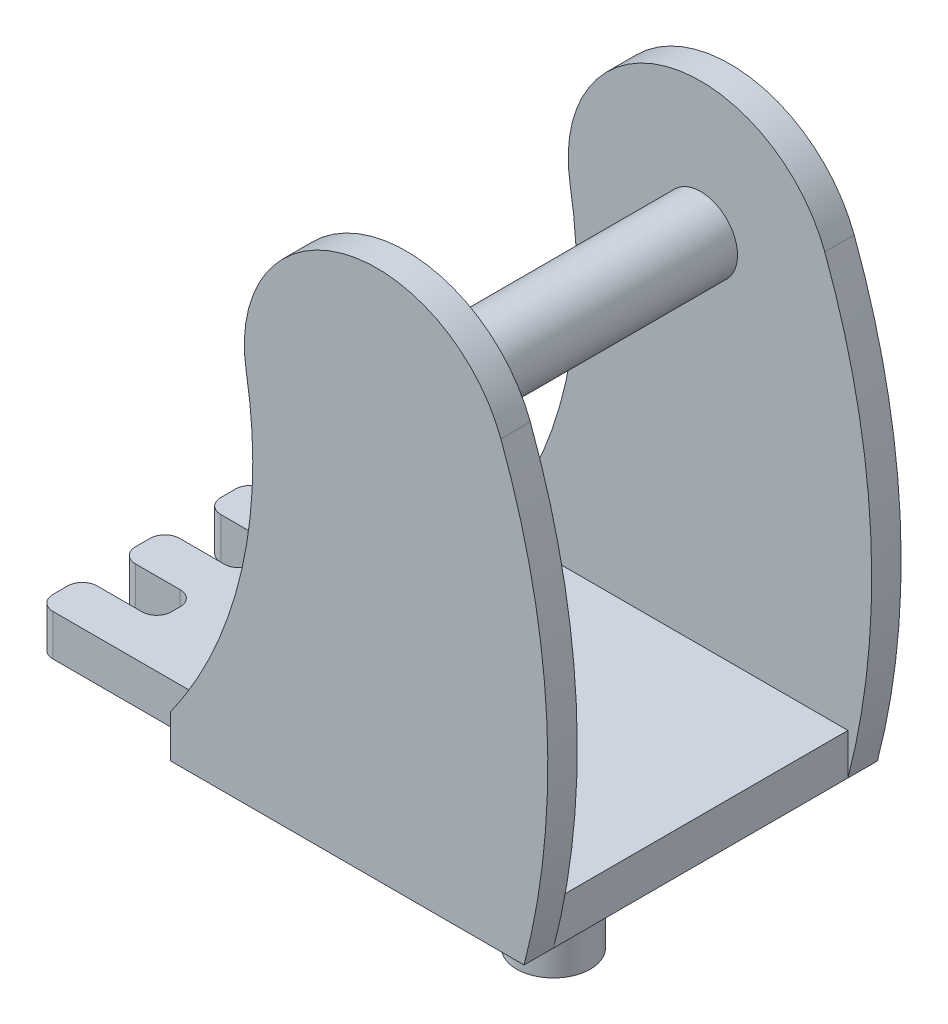
SolidWorks part; units mm, degrees
ref_plane "Front Plane" through (0, 0, 0) normal (0, 0, 1) x (1, 0, 0)
ref_plane "Top Plane" through (0, 0, 0) normal (0, 1, 0) x (1, 0, 0)
ref_plane "Right Plane" through (0, 0, 0) normal (1, 0, 0) x (0, 0, -1)
sketch "Sketch1" plane through (0, 0, 0) normal (0, 0, 1) x (1, 0, 0)
  circle A0 centre (0, 0) radius 12.5
  dimension "D1" = 25
extrude "Boss-Extrude1" add sketch "Sketch1" along normal mid plane 100
sketch "Sketch2" plane through (0, 0, 50) normal (0, 0, 1) x (1, 0, 0)
  line L0 (0, 0) -> (0, -135) construction
  line L1 (0, -135) -> (50, -135)
  line L2 (0, -135) -> (-70, -135)
  line L3 (-70, -120.4597) -> (-70, -135)
  arc A0 (42.1321, 15.8077) -> (-44.3389, -7.6849) centre (0, 0) ccw
  arc A1 (50, -135) -> (42.1321, 15.8077) centre (-191.9352, -72.013) ccw
  arc A2 (-44.3389, -7.6849) -> (-70, -120.4597) centre (-192.2863, -33.3275) cw
  dimension "D1" = 90
  dimension "D5" = 250
  dimension "D2" = 135
  dimension "D3" = 50
  dimension "D4" = 70
extrude "Boss-Extrude2" add sketch "Sketch2" along normal blind 10
ref_axis "Axis1" through (0, 0, 50) along (0, 0, -1)
mirror "Mirror1" about plane through (0, 0, 0) normal (0, 0, 1) of "Boss-Extrude2"
ref_plane "Plane1" through (0, -135, 0) normal (0, -1, 0) x (-1, 0, 0)
sketch "Sketch3" plane through (0, -135, 0) normal (0, -1, 0) x (-1, 0, 0)
  line L0 (120, 7) -> (104.7741, 7)
  line L1 (99.7741, 2) -> (99.7741, -2)
  line L2 (120, 50) -> (-50, 50)
  line L3 (120, -50) -> (-50, -50)
  line L4 (-50, 50) -> (-50, -50)
  line L5 (125, 45) -> (125, 40)
  line L7 (120, -7) -> (104.7741, -7)
  line L8 (120, 35) -> (104.7741, 35)
  line L10 (120, 22) -> (104.7741, 22)
  line L11 (99.7741, 30) -> (99.7741, 27)
  line L12 (99.7741, -27) -> (99.7741, -30)
  line L14 (120, -35) -> (104.7741, -35)
  line L15 (120, -22) -> (104.7741, -22)
  line L16 (125, 17) -> (125, 12)
  line L17 (125, -12) -> (125, -17)
  line L18 (125, -40) -> (125, -45)
  arc A0 (120, -50) -> (125, -45) centre (120, -45) ccw
  arc A1 (125, -40) -> (120, -35) centre (120, -40) ccw
  arc A2 (99.7741, -30) -> (104.7741, -35) centre (104.7741, -30) ccw
  arc A3 (99.7741, -27) -> (104.7741, -22) centre (104.7741, -27) cw
  arc A4 (125, -17) -> (120, -22) centre (120, -17) cw
  arc A5 (125, -12) -> (120, -7) centre (120, -12) ccw
  arc A6 (99.7741, -2) -> (104.7741, -7) centre (104.7741, -2) ccw
  arc A7 (104.7741, 7) -> (99.7741, 2) centre (104.7741, 2) ccw
  arc A8 (120, 7) -> (125, 12) centre (120, 12) ccw
  arc A9 (125, 17) -> (120, 22) centre (120, 17) ccw
  arc A10 (104.7741, 22) -> (99.7741, 27) centre (104.7741, 27) cw
  arc A11 (104.7741, 35) -> (99.7741, 30) centre (104.7741, 30) ccw
  arc A12 (120, 35) -> (125, 40) centre (120, 40) ccw
  arc A13 (120, 50) -> (125, 45) centre (120, 45) cw
  point P18 (125, -50)
  point P23 (99.7741, -35)
  point P26 (99.7741, -22)
  point P33 (99.7741, -7)
  point P36 (99.7741, 7)
  point P43 (99.7741, 22)
  point P46 (99.7741, 35)
  point P51 (125, 50)
  dimension "D10" = 5
  dimension "D1" = 175
  dimension "D2" = 175
  dimension "D3" = 15
  dimension "D4" = 15
  dimension "D5" = 15
  dimension "D6" = 15
  dimension "D7" = 13
  dimension "D8" = 14
  dimension "D9" = 13
extrude "Boss-Extrude3" add sketch "Sketch3" against normal blind 14 contours L2 L4 L3 A0 L18 A1 L14 A2 L12 A3 L15 A4 L17 A5 L7 A6 L1 A7 L0 A8 L16 A9 L10 A10 L11 A11 L8 A12 L5 A13
sketch "Sketch4" plane through (0, -135, 0) normal (0, -1, 0) x (-1, 0, 0)
  circle A0 centre (0, 0) radius 12.5
  dimension "D1" = 25
extrude "Boss-Extrude4" add sketch "Sketch4" along normal blind 50
